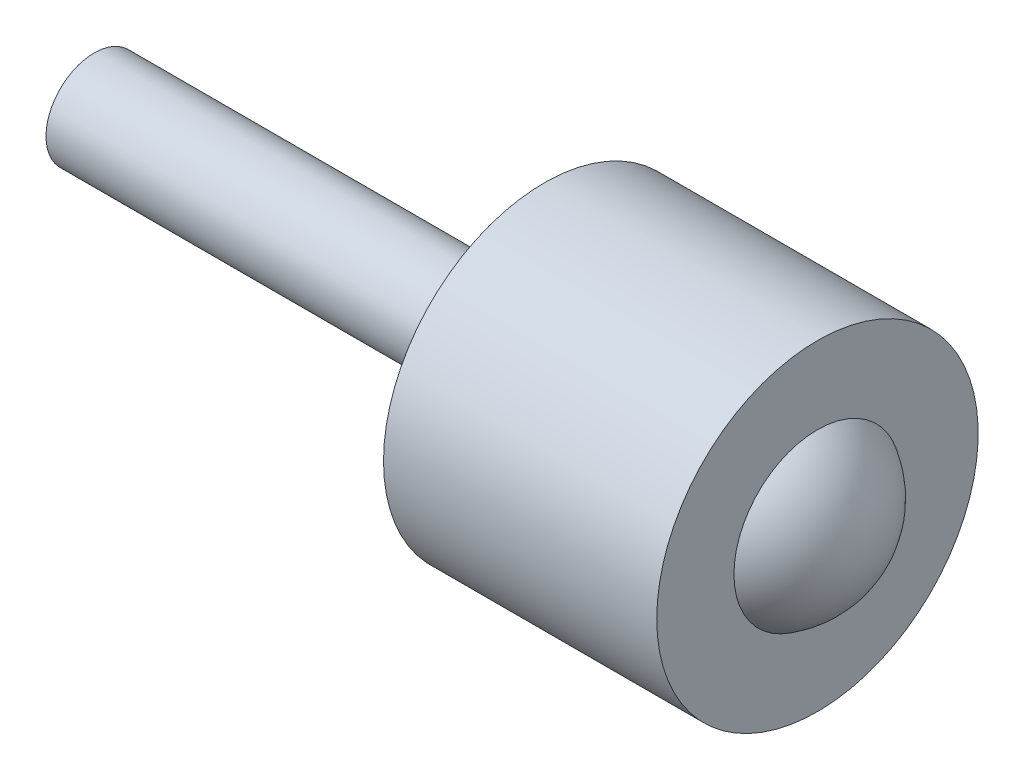
SolidWorks part; units mm, degrees
ref_plane "Front Plane" through (0, 0, 0) normal (0, 0, 1) x (1, 0, 0)
ref_plane "Top Plane" through (0, 0, 0) normal (0, 1, 0) x (1, 0, 0)
ref_plane "Right Plane" through (0, 0, 0) normal (1, 0, 0) x (0, 0, -1)
ref_axis "Axis1" through (-2.4, 0, 0) along (1, 0, 0)
sketch "Sketch1" plane through (0, 0, 0) normal (0, 0, 1) x (1, 0, 0)
  line L0 (0, 0) -> (48, 0)
  line L1 (0, 0) -> (0, 3)
  line L2 (0, 3) -> (28, 3)
  line L3 (28, 3) -> (28, 10)
  line L4 (28, 10) -> (45, 10)
  line L5 (45, 10) -> (45, 5.1962)
  arc A0 (48, 0) -> (45, 5.1962) centre (42, 0) ccw
  point P9 (33.8352, 1.3515)
  point P10 (0, 0)
  dimension "D7" = 6
  dimension "D1" = 17
  dimension "D2" = 28
  dimension "D3" = 3
  dimension "D4" = 10
  dimension "D5" = 3
revolve "Revolve1" add sketch "Sketch1" angle 360 about axis through (-2.4, 0, 0) along (1, 0, 0)
